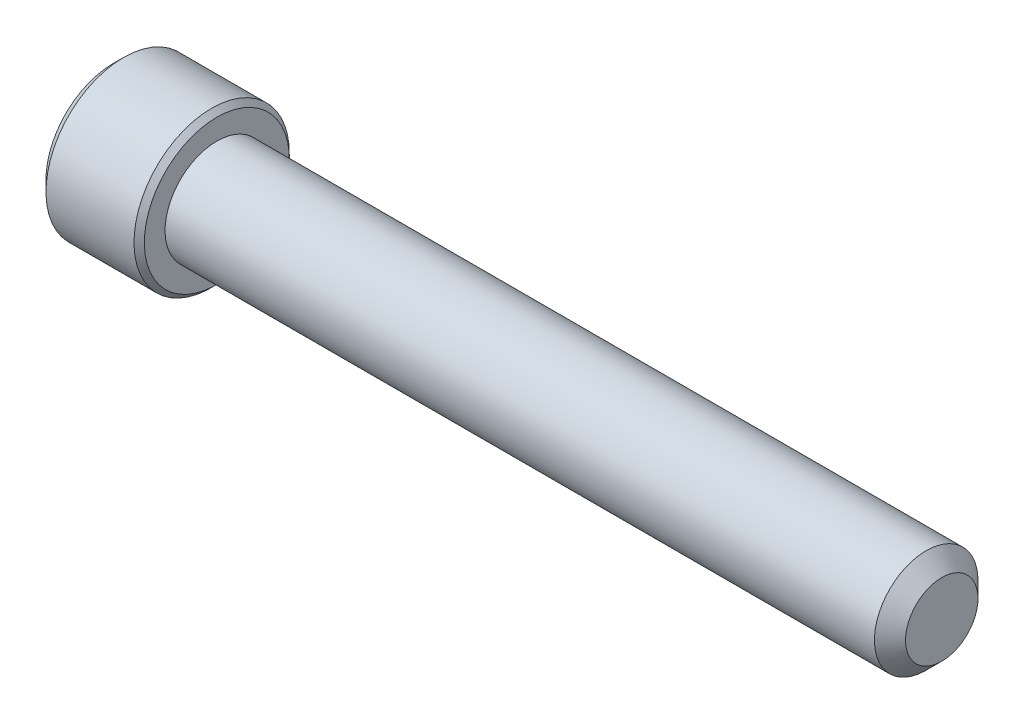
SolidWorks part; units mm, degrees
ref_plane "Front Plane" through (0, 0, 0) normal (0, 0, 1) x (1, 0, 0)
ref_plane "Top Plane" through (0, 0, 0) normal (0, 1, 0) x (1, 0, 0)
ref_plane "Right Plane" through (0, 0, 0) normal (1, 0, 0) x (0, 0, -1)
sketch "Sketch1" plane through (0, 0, 0) normal (0, 0, 1) x (1, 0, 0)
  line L0 (22.225, 0) -> (-22.225, 0) construction
  line L1 (22.225, 3.175) -> (22.225, -3.175) construction
  line L2 (-22.225, 4.445) -> (-22.225, -4.445) construction
  line L3 (-22.5425, 4.7625) -> (-27.94, 4.7625) construction
  line L4 (-27.94, 4.7625) -> (-28.575, 4.1275) construction
  line L5 (-28.575, 4.1275) -> (-28.575, -4.1275) construction
  line L6 (-28.575, -4.1275) -> (-27.94, -4.7625) construction
  line L7 (-27.94, -4.7625) -> (-22.5425, -4.7625) construction
  line L8 (-22.5425, 4.7625) -> (-22.225, 4.445) construction
  line L9 (-22.225, -4.445) -> (-22.5425, -4.7625) construction
  point P5 (-22.225, 4.7625)
  point P6 (-22.225, -4.7625)
  point P7 (-25.527, 0)
  point P12 (17.145, -3.175)
  dimension "D1" = 45
  dimension "Dec." = 6.35
  dimension "Length" = 44.45
  dimension "Head Dia" = 9.525
  dimension "Head Height" = 6.35
  dimension "Hex Depth" = 3.048
  dimension "Chamfer" = 0.635
  dimension "D2" = 5.08
  dimension "D3" = 0.3175
  dimension "D4" = 45
ref_plane "Plane1" through (22.225, 0, 0) normal (1, 0, 0) x (0, 0, -1)
ref_plane "Plane2" through (-28.575, 0, 0) normal (1, 0, 0) x (0, 0, -1)
sketch "Sketch2" plane through (22.225, 0, 0) normal (1, 0, 0) x (0, 0, -1)
  circle A0 centre (0, 0) radius 3.175
extrude "Boss-Extrude1" add sketch "Sketch2" against normal up to vertex (44.45 mm away) up to point (-22.225, 0, 0)
sketch "Sketch3" plane through (22.225, 0, 0) normal (1, 0, 0) x (0, 0, -1)
  circle A0 centre (0, 0) radius 3.175 construction
  circle A1 centre (0, 0) radius 3.175
curve "Helix/Spiral1" pitch 1.27 height 45.72 turns 36 parameters "Pitch"=1.27
chamfer "Chamfer1" distance 0.9525 angle 45 1 edges at (22.225, 0, -3.175)
sketch "Sketch5" plane through (0, 0, 0) normal (0, 0, 1) x (1, 0, 0)
  line L0 (21.6694, 3.175) -> (22.7806, 3.175)
  line L1 (22.7806, 3.175) -> (22.3044, 2.3501)
  line L2 (22.3044, 2.3501) -> (22.1456, 2.3501)
  line L3 (22.1456, 2.3501) -> (21.6694, 3.175)
  line L4 (22.225, 2.3501) -> (22.225, 3.175) construction
  line L5 (21.9075, 2.7626) -> (22.5425, 2.7626) construction
  dimension "D1" = 60
  dimension "D2" = 0.635
  dimension "D3" = 0.1588
sweep "Cut-Sweep1" [suppressed] cut profiles "Sketch5" path "Helix/Spiral1"
sketch "Sketch4" plane through (-28.575, 0, 0) normal (1, 0, 0) x (0, 0, -1)
  line L0 (-4.7625, 0.7937) -> (4.7625, 0.7937) construction
  line L1 (0, 2.7496) -> (-2.3812, 1.3748)
  line L2 (-2.3812, 1.3748) -> (-2.3812, -1.3748)
  line L3 (-2.3812, -1.3748) -> (0, -2.7496)
  line L4 (0, -2.7496) -> (2.3813, -1.3748)
  line L5 (2.3813, -1.3748) -> (2.3812, 1.3748)
  line L6 (2.3812, 1.3748) -> (0, 2.7496)
  line L7 (0, 0) -> (0, 0.7937) construction
  circle A0 centre (0, 0) radius 2.3813 construction
  dimension "Hex Size" = 4.7625
  dimension "D1" = 9.525
  dimension "D2" = 0.7937
sketch "Sketch6" plane through (0, 0, 0) normal (0, 0, 1) x (1, 0, 0)
  line L0 (-27.94, 4.7625) -> (-28.575, 4.1275) construction
  line L2 (-22.225, 4.445) -> (-22.225, -4.445) construction
  line L3 (-28.575, 4.1275) -> (-28.575, -4.1275) construction
  line L4 (-27.94, 4.7625) -> (-28.575, 4.1275)
  line L5 (-22.5425, 4.7625) -> (-27.94, 4.7625) construction
  line L6 (-22.225, 4.445) -> (-22.225, 0)
  line L7 (-28.575, 4.1275) -> (-28.575, 0)
  line L8 (-22.225, 0) -> (-28.575, 0) construction
  line L9 (-22.225, 0) -> (-28.575, 0)
  line L10 (-22.5425, 4.7625) -> (-22.225, 4.445) construction
  line L11 (-22.5425, 4.7625) -> (-27.94, 4.7625)
  line L12 (-22.5425, 4.7625) -> (-22.225, 4.445)
revolve "Revolve1" add sketch "Sketch6" angle 360 about L8
extrude "Cut-Extrude1" cut sketch "Sketch4" along normal up to vertex (3.048 mm away) up to point (-25.527, 0, 0)
sketch "Sketch8" plane through (-28.575, 0, 0) normal (-1, 0, 0) x (0, 0, 1)
  circle A1 centre (0, 0) radius 2.7496
extrude "Cut-Extrude2" cut sketch "Sketch8" against normal blind 1.27 draft 45
equation "\"D3@Helix/Spiral1\" = \"Length@Sketch1\"+\"Pitch@Helix/Spiral1\""
equation "\"D3@Sketch5\" = \"Pitch@Helix/Spiral1\"*.125"
equation "\"D2@Sketch5\" = \"Pitch@Helix/Spiral1\"*.50"
equation "\"D1@Chamfer1\" = \"Pitch@Helix/Spiral1\"*.75"
equation "\"D2@Sketch1\" = \"Pitch@Helix/Spiral1\"*4"
equation "\"D1@Sketch4\" = \"Head Dia@Sketch1\""
equation "\"Chamfer@Sketch1\" = \"Head Height@Sketch1\"/10"
equation "\"D3@Sketch1\" = \"Chamfer@Sketch1\"/2"
equation "\"D1@Cut-Extrude2\" = \"Chamfer@Sketch1\"*2"
